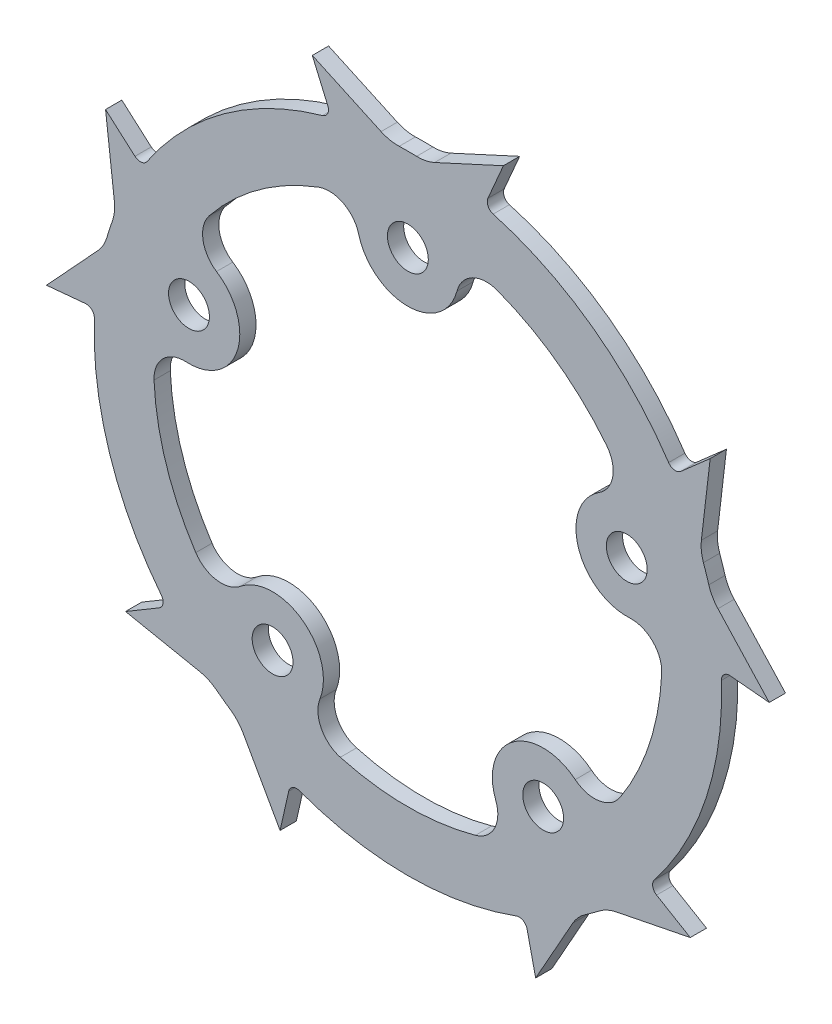
SolidWorks part; units mm, degrees
material "Alloy Steel (SS)"
ref_plane "Front Plane" through (0, 0, 0) normal (0, 0, 1) x (1, 0, 0)
ref_plane "Top Plane" through (0, 0, 0) normal (0, 1, 0) x (1, 0, 0)
ref_plane "Right Plane" through (0, 0, 0) normal (1, 0, 0) x (0, 0, -1)
sketch "Sketch1" plane through (0, 0, 0) normal (0, 0, 1) x (1, 0, 0)
  line L0 (0, 0) -> (0, 28.7588) construction
  line L1 (0, 0) -> (27.3512, 8.8869) construction
  line L2 (0, 0) -> (16.904, -23.2663) construction
  line L3 (0, 0) -> (-16.904, -23.2663) construction
  line L4 (0, 0) -> (-27.3512, 8.8869) construction
  line L5 (-9.5364, 38.0223) -> (-11.938, 43.595)
  line L6 (-11.938, 43.595) -> (0, 0) construction
  line L7 (-11.938, 43.595) -> (-3.3492, 39.6472)
  line L8 (0, 0) -> (0, 45.2) construction
  line L9 (9.5364, 38.0223) -> (11.938, 43.595)
  line L10 (11.938, 43.595) -> (3.3492, 39.6472)
  line L11 (-10.3533, 37.8081) -> (13.7846, 44.4179) construction
  line L12 (-11.938, 43.595) -> (-5.2258, 45.4331) construction
  circle A0 centre (0, 0) radius 45.2 construction
  circle A1 centre (0, 0) radius 31.75
  circle A2 centre (0, 28.7588) radius 2.5527
  arc A3 (6.1383, 27.1326) -> (-6.1383, 27.1326) centre (0, 28.7588) cw
  arc A4 (6.1383, 27.1326) -> (11.1605, 29.7238) centre (9.8212, 26.157) cw
  arc A5 (-6.1383, 27.1326) -> (-11.1605, 29.7238) centre (-9.8212, 26.157) ccw
  arc A6 (23.9079, 14.2223) -> (24.8203, 19.7994) centre (21.8418, 17.4235) ccw
  arc A7 (27.7015, 2.5466) -> (23.9079, 14.2223) centre (27.3512, 8.8869) cw
  circle A8 centre (27.3512, 8.8869) radius 2.5527
  arc A9 (27.7015, 2.5466) -> (31.7178, -1.4291) centre (27.9117, -1.2576) cw
  arc A10 (20.9141, -18.3428) -> (26.5002, -17.4871) centre (23.3202, -15.3887) ccw
  arc A11 (10.9822, -25.5588) -> (20.9141, -18.3428) centre (16.904, -23.2663) cw
  circle A12 centre (16.904, -23.2663) radius 2.5527
  arc A13 (10.9822, -25.5588) -> (8.4422, -30.607) centre (7.4292, -26.9342) cw
  arc A14 (-10.9822, -25.5588) -> (-8.4422, -30.607) centre (-7.4292, -26.9342) ccw
  arc A15 (-20.9141, -18.3428) -> (-10.9822, -25.5588) centre (-16.904, -23.2663) cw
  circle A16 centre (-16.904, -23.2663) radius 2.5527
  arc A17 (-20.9141, -18.3428) -> (-26.5002, -17.4871) centre (-23.3202, -15.3887) cw
  arc A18 (-27.7015, 2.5466) -> (-31.7178, -1.4291) centre (-27.9117, -1.2576) ccw
  arc A19 (-23.9079, 14.2223) -> (-27.7015, 2.5466) centre (-27.3512, 8.8869) cw
  circle A20 centre (-27.3512, 8.8869) radius 2.5527
  arc A21 (-23.9079, 14.2223) -> (-24.8203, 19.7994) centre (-21.8418, 17.4235) cw
  circle A22 centre (0, 0) radius 39.2
  arc A23 (-3.3492, 39.6472) -> (-1.0868, 39.1849) centre (-1.2276, 44.263) ccw
  arc A24 (3.3492, 39.6472) -> (1.0868, 39.1849) centre (1.2276, 44.263) cw
  point P47 (0, 0)
  dimension "D1" = 90.4
  dimension "D2" = 63.5
  dimension "D3" = 5.1054
  dimension "D4" = 28.7588
  dimension "D6" = 6.35
  dimension "D8" = 6
  dimension "D12" = 5.08
  dimension "D10" = 40
  dimension "D7" = 3.81
  dimension "D9" = 8
  dimension "D11" = 23.876
  dimension "D5" = 5
extrude "Boss-Extrude1" add sketch "Sketch1" along normal blind 2.032 contours A0 A1 | A19 A21 A1 A18 A20 | A5 A3 A4 A1 A2 | A7 A9 A1 A6 A8 | A11 A13 A1 A10 A12 | A15 A17 A1 A14 A16 region at (-5.1922, 37.7357, 0) region at (31.7182, -0.7142, 0) region at (7.9633, 29.7579, 0) region at (18.529, -25.503, 0) region at (-25.8367, 16.7699, 0) region at (-18.529, -25.503, 0)
extrude "Boss-Extrude5" add sketch "Sketch1<5>" along normal up to surface (2.032 mm away) contours L7 L5 A22 | A22 L9 L10 region at (-7.9556, 40.3115, 0) region at (7.9556, 40.3115, 0) up to face at (0, 0, 2.032)
sketch "Sketch1<5>" plane through (0, 0, 0) normal (0, 0, 1) x (1, 0, 0) same geometry as "Sketch1"
fillet "Fillet2" radius 1.016 2 edges at (9.5364, 38.0223, 1.016) (-9.5364, 38.0223, 1.016)
pattern_circular "CirPattern2" count 5 over 360 about axis through (0, 0, 2.032) along (0, 0, 1) of "Boss-Extrude5", "Fillet2"
